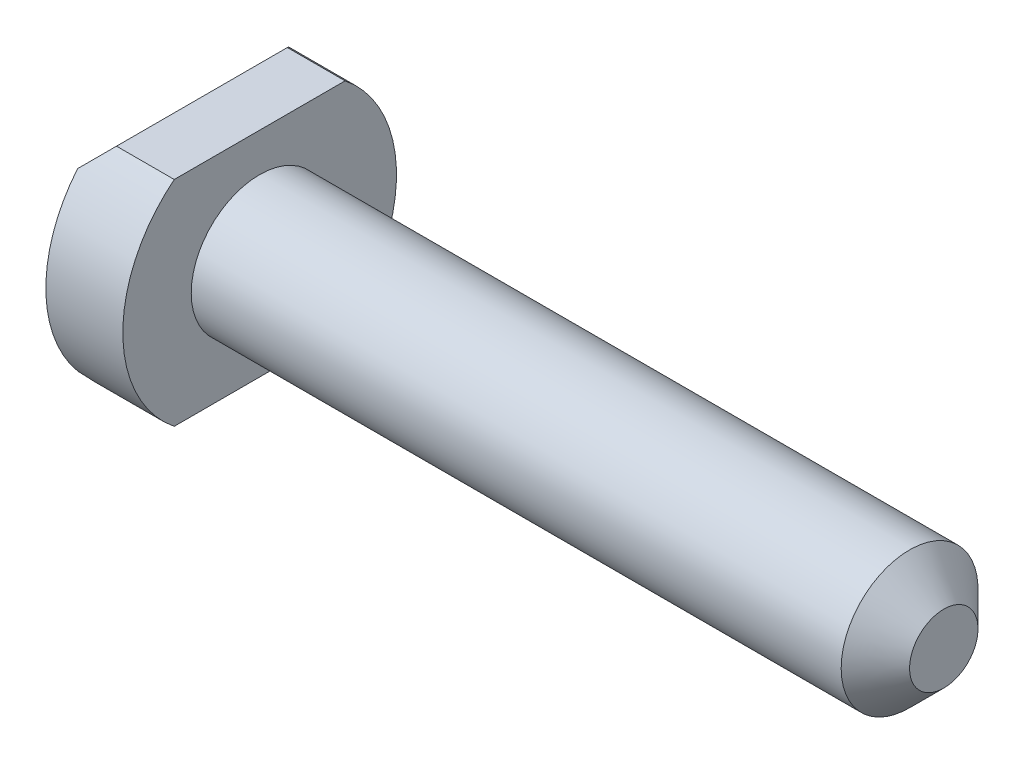
SolidWorks part; units mm, degrees
ref_plane "Front Plane" through (0, 0, 0) normal (0, 0, 1) x (1, 0, 0)
ref_plane "Top Plane" through (0, 0, 0) normal (0, 1, 0) x (1, 0, 0)
ref_plane "Right Plane" through (0, 0, 0) normal (1, 0, 0) x (0, 0, -1)
sketch "BaseHeadSke" plane through (0, 0, 0) normal (1, 0, 0) x (0, 0, -1)
  line L0 (-25.8903, 0) -> (25.0813, 0) construction
  line L1 (0, 0) -> (0, 16) construction
  line L2 (-9.9875, 12.5) -> (9.9875, 12.5)
  line L3 (-9.9875, -12.5) -> (9.9875, -12.5)
  arc A0 (-9.9875, 12.5) -> (-9.9875, -12.5) centre (0, 0) ccw
  arc A1 (9.9875, -12.5) -> (9.9875, 12.5) centre (0, 0) ccw
  dimension "Nominal_Size" = 16
extrude "BaseHead" add sketch "BaseHeadSke" along normal blind 9
chamfer "HeadChamfer" distance 2.25 angle 45 2 edges at (0, -12.5, 0) (0, 12.5, 0)
sketch "BodySke" plane through (0, 0, 0) normal (0, 0, 1) x (1, 0, 0)
  line L0 (0, 0) -> (98.0537, 0) construction
  line L1 (0, 10.25) -> (0, -10.25) construction
  line L2 (85, 8) -> (89, 4)
  line L3 (0, 0) -> (89, 0)
  line L4 (0, 0) -> (0, 8)
  line L5 (0, 8) -> (85, 8)
  line L6 (89, 0) -> (89, 4)
  line L7 (9, -12.5) -> (9, 12.5) construction
  line L8 (34, 0) -> (34, 11.0908) construction
  line L9 (11, 0) -> (11, 16.7727) construction
  line L10 (29, 0) -> (29, 8) construction
  point P14 (0, 6.8985)
  dimension "D1" = 5
  dimension "Thread_minor" = 13.797
  dimension "Advance" = 2
revolve "BaseBody" add sketch "BodySke" angle 360 about L0
cosmetic thread "ThreadCosmetic" [suppressed] parameters "Thread_length"=51, "Thread_minor"=13.797
sketch "BoltSke" plane through (0, 0, 0) normal (0, 0, 1) x (1, 0, 0)
  line L0 (0, 0) -> (90.6713, 0) construction
  line L1 (0, 0) -> (98.0537, 0) construction
  line L2 (9, 0) -> (9, 8)
  line L5 (9, -12.5) -> (9, 12.5) construction
  line L7 (9, 8) -> (29, 8)
  line L11 (9, 0) -> (29, 0)
  line L12 (29, 8) -> (29, 0)
  line L13 (29, 0) -> (29, 8) construction
  dimension "Nominal_Size" = 16
revolve "Bolt" add sketch "BoltSke" angle 360 about L0
sketch "ThdSchSke" plane through (0, 0, 0) normal (0, 0, 1) x (1, 0, 0)
  line L0 (0, 0) -> (92.3539, 0) construction
  line L1 (0, 0) -> (98.0537, 0) construction
  line L2 (83, 9.2719) -> (83, 8)
  line L3 (83, 9.2719) -> (84.2719, 9.2719)
  line L4 (84.2719, 9.2719) -> (84.2719, 8)
  line L5 (84.2719, 8) -> (83.636, 6.8985)
  line L6 (83.636, 6.8985) -> (83, 8)
  dimension "D1" = 2
revolve "ThreadSchematic" [suppressed] cut sketch "ThdSchSke" angle 360 about L0
pattern_linear "ThdSchPat" [suppressed] of bodies 116
equation "\"D1@HeadChamfer\" = \"Head_height@BaseHead\" * 0.25"
equation "\"D1@BodySke\" = 2.5 * \"Advance@BodySke\""
equation "\"Thread_minor@ThreadCosmetic\" = \"Thread_minor@BodySke\""
equation "\"Thread_length@ThreadCosmetic\" = \"Thread_length@BodySke\" - \"Chamfer_end_width@BodySke\""
equation "\"D1@ThdSchSke\" = \"Advance@BodySke\""
equation "\"Nominal_Size@BoltSke\" = \"Nominal_Size@BaseHeadSke\""
equation "\"Advance@ThdSchPat\" = \"Advance@BodySke\""
equation "\"Tooth_Num@ThdSchPat\" =  int( (  \"Thread_length@BodySke\" - \"Chamfer_end_width@BodySke\" )  / \"Advance@BodySke\" ) "
